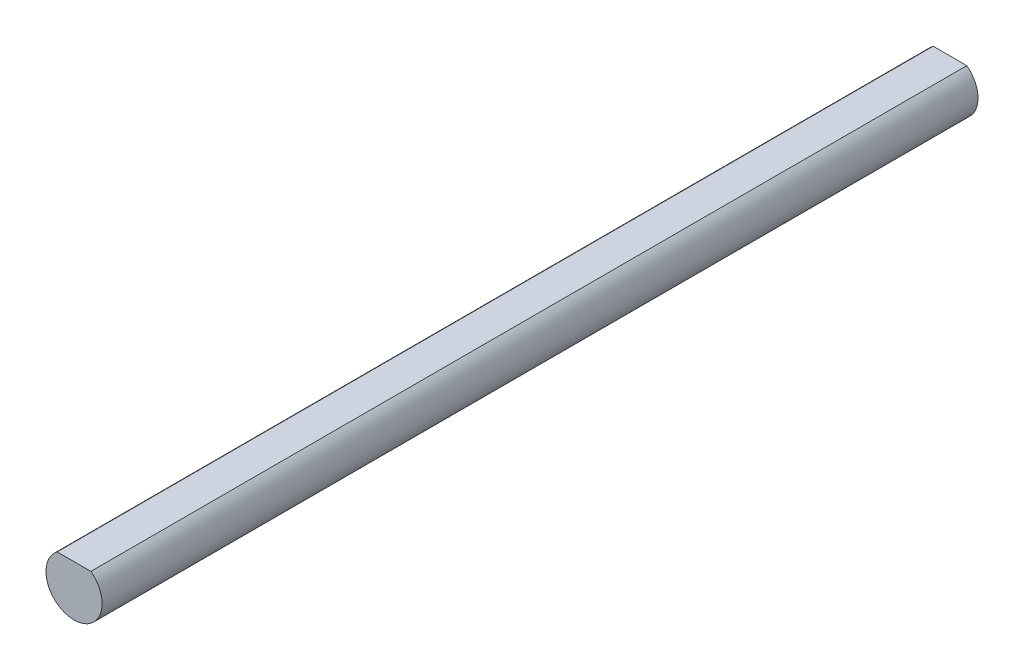
SolidWorks part; units mm, degrees
material "Stainless Steel (ferritic)"
ref_plane "Front Plane" through (0, 0, 0) normal (0, 0, 1) x (1, 0, 0)
ref_plane "Top Plane" through (0, 0, 0) normal (0, 1, 0) x (1, 0, 0)
ref_plane "Right Plane" through (0, 0, 0) normal (1, 0, 0) x (0, 0, -1)
sketch "Sketch1" plane through (0, 0, 0) normal (0, 0, 1) x (1, 0, 0)
  circle A0 centre (0, 0) radius 5
extrude "Boss-Extrude1" add sketch "Sketch1" along normal blind 78 and the other way blind 78
sketch "Sketch2" plane through (0, 0, 78) normal (0, 0, 1) x (1, 0, 0)
  line L0 (-3, 4) -> (3, 4)
  circle A1 centre (0, 0) radius 5 construction
  arc A2 (-3, 4) -> (3, 4) centre (0, 0) cw
  dimension "D1" = 4
extrude "Cut-Extrude1" cut sketch "Sketch2" against normal blind 156
